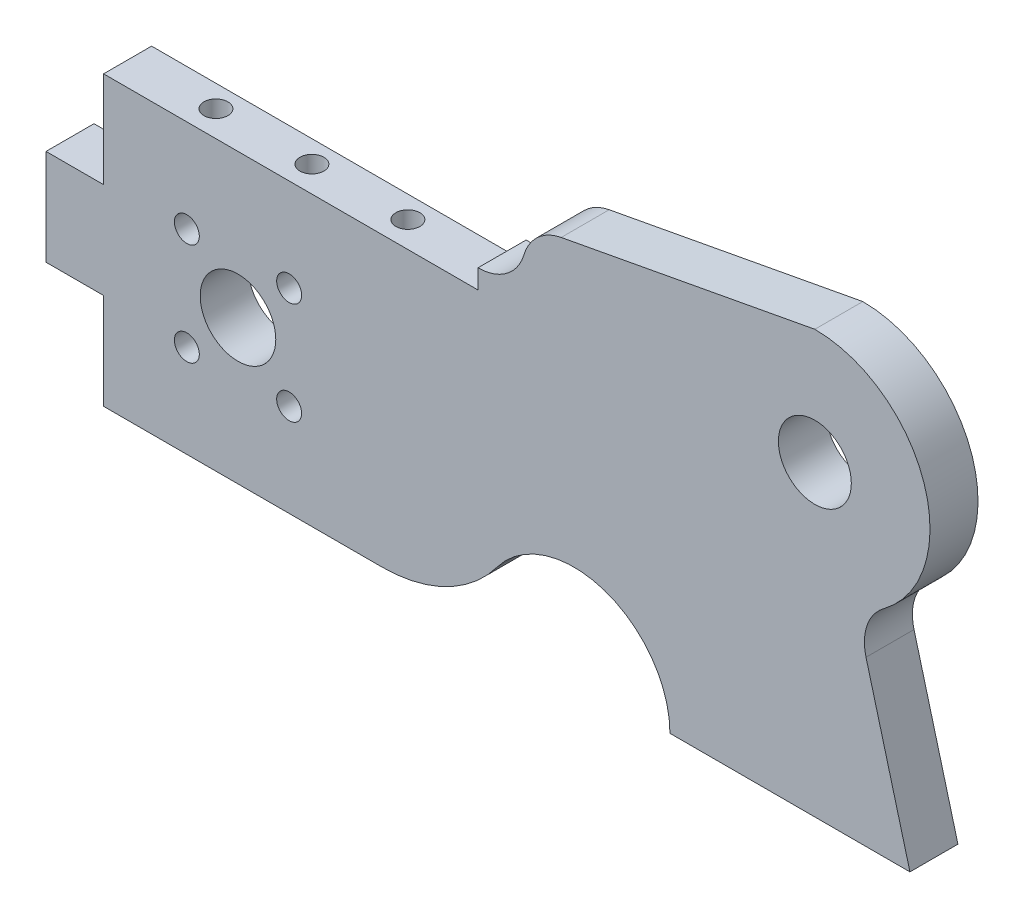
SolidWorks part; units mm, degrees
ref_plane "Front Plane" through (0, 0, 0) normal (0, 0, 1) x (1, 0, 0)
ref_plane "Top Plane" through (0, 0, 0) normal (0, 1, 0) x (1, 0, 0)
ref_plane "Right Plane" through (0, 0, 0) normal (1, 0, 0) x (0, 0, -1)
sketch "Sketch1" plane through (0, 0, 0) normal (0, 0, 1) x (1, 0, 0)
  line L0 (0, 0) -> (107.95, 0)
  line L3 (0, 38.1) -> (0, 25.4)
  line L4 (95.3675, 55.88) -> (0, 38.1)
  line L5 (0, 19.05) -> (100.2273, 19.05) construction
  line L6 (19.05, 19.05) -> (19.05, 28.62) construction
  line L7 (19.05, 19.05) -> (25.817, 25.817) construction
  line L8 (107.95, 0) -> (100.9363, 26.1756)
  line L10 (0, 12.7) -> (0, 0)
  line L11 (0, 25.4) -> (-6.35, 25.4)
  line L13 (0, 12.7) -> (-6.35, 12.7)
  line L14 (-6.35, 25.4) -> (-6.35, 12.7)
  line L15 (100.9363, 26.1756) -> (100.8688, 26.4276)
  arc A0 (100.8688, 26.4276) -> (95.3675, 55.88) centre (95.3675, 40.64) ccw
  circle A1 centre (95.3675, 40.64) radius 4.826
  circle A2 centre (19.05, 19.05) radius 9.57 construction
  circle A3 centre (25.817, 25.817) radius 1.651
  circle A4 centre (25.817, 12.283) radius 1.651
  circle A5 centre (12.283, 12.283) radius 1.651
  circle A6 centre (12.283, 25.817) radius 1.651
  point P26 (19.05, 19.05)
  dimension "D1" = 9.652
  dimension "D5" = 15.24
  dimension "D4" = 19.14
  dimension "D7" = 3.302
  dimension "D11" = 97.0107
  dimension "D2" = 38.1
  dimension "D3" = 40.64
  dimension "D6" = 107.95
  dimension "D8" = 45
  dimension "D9" = 4
  dimension "D10" = 19.05
  dimension "D12" = 75
  dimension "D14" = 12.7
  dimension "D15" = 12.7
  dimension "D16" = 6.35
extrude "Boss-Extrude1" add sketch "Sketch1" along normal blind 6.35
sketch "Sketch2" plane through (0, 0, 6.35) normal (0, 0, 1) x (1, 0, 0)
  circle A0 centre (95.3675, 40.64) radius 38.1 construction
sketch "Sketch3" plane through (0, 0, 0) normal (-1, 0, 0) x (0, 0, 1)
  line L0 (0, 38.1) -> (6.35, 25.4) construction
  line L1 (6.35, 12.7) -> (0, 0) construction
  circle A0 centre (3.175, 31.75) radius 1.5875
  circle A1 centre (3.175, 6.35) radius 1.5875
  dimension "D1" = 3.175
  dimension "D2" = 3.175
extrude "Cut-Extrude1" cut sketch "Sketch3" against normal blind 6.35
sketch "Sketch6" plane through (0, 0, 6.35) normal (0, 0, 1) x (1, 0, 0)
  line L0 (0, 0) -> (107.95, 0) construction
  line L1 (50.8, 0) -> (76.2, 0)
  arc A0 (76.2, 0) -> (50.8, 0) centre (63.5, 0) ccw
  dimension "D1" = 25.4
  dimension "D2" = 31.75
extrude "Cut-Extrude2" cut sketch "Sketch6" against normal blind 6.35
sketch "Sketch7" plane through (0, 0, 6.35) normal (0, 0, 1) x (1, 0, 0)
  line L0 (12.283, 25.817) -> (25.817, 12.283) construction
  line L1 (12.283, 12.283) -> (25.817, 25.817) construction
  circle A0 centre (19.05, 19.05) radius 5
  dimension "D1" = 10
extrude "Cut-Extrude3" cut sketch "Sketch7" against normal through all
fillet "Fillet1" radius 6.35 1 edges at (100.8688, 26.4276, 3.175)
sketch "Sketch8" plane through (0, 0, 6.35) normal (0, 0, 1) x (1, 0, 0)
  line L1 (0, 38.1) -> (50.8, 38.1)
  line L2 (0, 38.1) -> (0, 50.8)
  line L3 (0, 50.8) -> (50.8, 50.8)
  line L4 (50.8, 38.1) -> (50.8, 50.8)
  dimension "D1" = 50.8
  dimension "D2" = 12.7
extrude "Cut-Extrude4" cut sketch "Sketch8" against normal blind 50.8
sketch "Sketch9" plane through (0, 0, 6.35) normal (0, 0, 1) x (1, 0, 0)
  line L3 (50.8, 40.64) -> (57.15, 40.64)
  line L5 (57.15, 40.64) -> (50.8, 40.64)
  line L6 (57.15, 40.64) -> (57.15, 50.8)
  line L7 (57.15, 50.8) -> (50.8, 50.8)
  line L8 (50.8, 40.64) -> (50.8, 50.8)
  line L9 (0, 38.1) -> (50.8, 38.1) construction
  line M8 (50.8, 47.571) -> (50.8, 38.1)
  line M21 (95.3675, 55.88) -> (50.8, 47.571)
  dimension "D1" = 10.16
  dimension "D2" = 2.54
  dimension "D3" = 6.35
extrude "Cut-Extrude5" cut sketch "Sketch9" against normal blind 19.304 contours L3 L6 M21 M8 region at (54.0583, 44.4092, 6.35)
fillet "Fillet6" radius 6.35 1 edges at (57.15, 40.64, 3.175)
fillet "Fillet7" radius 6.35 1 edges at (57.15, 48.7549, 3.175)
fillet "Fillet8" radius 19.05 1 edges at (50.8, 0, 3.175)
sketch "Sketch10" plane through (0, 0, 0) normal (0, -1, 0) x (1, 0, 0)
  line L0 (76.2, 6.35) -> (107.95, 6.35) construction
  line L1 (0, 6.35) -> (0, 0) construction
  line L2 (0, 6.35) -> (38.1, 6.35) construction
  line L3 (107.95, 6.35) -> (107.95, 0) construction
  line L4 (76.2, 0) -> (76.2, 6.35) construction
  circle A0 centre (97.79, 3.175) radius 1.5875
  circle A1 centre (86.36, 3.175) radius 1.5875
  circle A2 centre (31.75, 3.175) radius 1.5875
  circle A3 centre (12.7, 3.175) radius 1.5875
  dimension "D1" = 3.175
  dimension "D2" = 3.175
  dimension "D3" = 3.175
  dimension "D4" = 3.175
  dimension "D5" = 12.7
  dimension "D6" = 19.05
  dimension "D7" = 10.16
  dimension "D8" = 10.16
  dimension "D9" = 11.43
  dimension "D10" = 3.175
  dimension "D11" = 3.175
extrude "Cut-Extrude6" cut sketch "Sketch10" against normal blind 6.35
sketch "Sketch11" plane through (0, 38.1, 0) normal (0, 1, 0) x (1, 0, 0)
  line L0 (0, -6.35) -> (0, 0) construction
  line L1 (50.8, 0) -> (50.8, -6.35) construction
  line L2 (0, -6.35) -> (50.8, -6.35) construction
  circle A0 centre (12.7, -2.9224) radius 1.5875
  circle A1 centre (25.4, -2.9224) radius 1.5875
  circle A2 centre (38.1, -2.9224) radius 1.5875
  dimension "D1" = 3.175
  dimension "D2" = 3.175
  dimension "D3" = 3.175
  dimension "D4" = 12.7
  dimension "D5" = 12.7
  dimension "D6" = 12.7
  dimension "D7" = 12.7
  dimension "D8" = 3.4276
extrude "Cut-Extrude7" cut sketch "Sketch11" against normal blind 6.35
sketch "Sketch12" plane through (0, 0, 6.35) normal (0, 0, 1) x (1, 0, 0)
  line L1 (0, 38.1) -> (1.27, 38.1)
  line L2 (0, 38.1) -> (0, 25.4)
  line L3 (0, 25.4) -> (1.27, 25.4)
  line L4 (1.27, 38.1) -> (1.27, 25.4)
  line L5 (0, 0) -> (1.27, 0)
  line L6 (0, 0) -> (0, 12.7)
  line L7 (0, 12.7) -> (1.27, 12.7)
  line L8 (1.27, 0) -> (1.27, 12.7)
  dimension "D1" = 12.7
  dimension "D2" = 12.7
  dimension "D3" = 1.27
  dimension "D4" = 1.27
extrude "Cut-Extrude8" cut sketch "Sketch12" against normal through all
